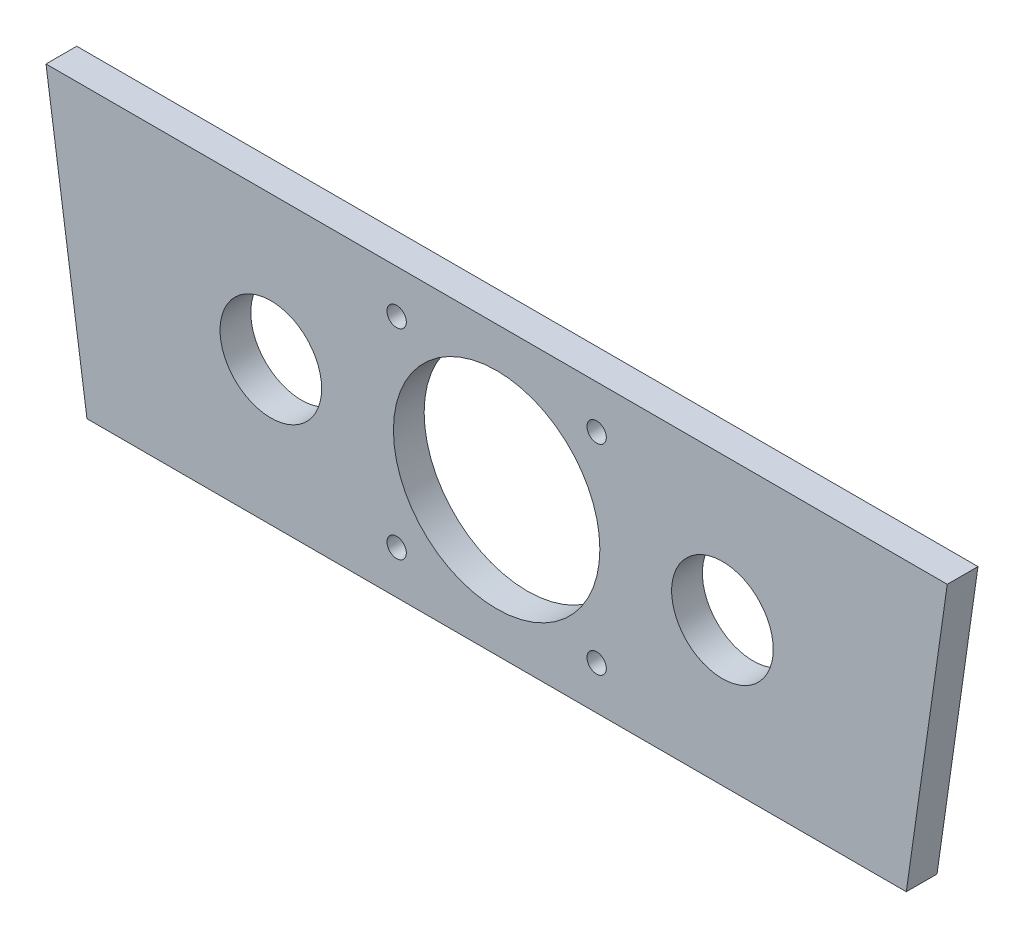
SolidWorks part; units mm, degrees
material "ASTM A36 Steel"
ref_plane "Front Plane" through (0, 0, 0) normal (0, 0, 1) x (1, 0, 0)
ref_plane "Top Plane" through (0, 0, 0) normal (0, 1, 0) x (1, 0, 0)
ref_plane "Right Plane" through (0, 0, 0) normal (1, 0, 0) x (0, 0, -1)
sketch "Sketch2" plane through (0, 0, 0) normal (0, 0, 1) x (1, 0, 0)
  line L0 (0, 0) -> (152.4, 0)
  line L1 (76.2, 0) -> (76.2, 6.35) construction
  line L2 (139.7, 6.35) -> (12.7, 6.35)
  line L3 (12.7, 6.35) -> (6.35, 50.8)
  line L4 (6.35, 50.8) -> (0, 50.8)
  line L5 (0, 50.8) -> (0, 0)
  line L6 (152.4, 50.8) -> (152.4, 0)
  line L7 (146.05, 50.8) -> (152.4, 50.8)
  line L8 (139.7, 6.35) -> (146.05, 50.8)
  line L9 (12.7, 6.35) -> (12.7, 0) construction
  line L10 (12.7, 6.35) -> (0, 6.35) construction
  line L11 (146.05, 50.8) -> (6.35, 50.8)
  line L12 (9.525, 28.575) -> (142.875, 28.575) construction
  line L13 (76.2, 50.8) -> (76.2, 6.35) construction
  line L14 (60.7, 13.075) -> (60.7, 28.575) construction
  line L15 (60.7, 13.075) -> (76.2, 13.075) construction
  circle A0 centre (60.7, 13.075) radius 1.5
  circle A1 centre (91.7, 13.075) radius 1.5
  circle A2 centre (60.7, 44.075) radius 1.5
  circle A3 centre (91.7, 44.075) radius 1.5
  circle A4 centre (76.2, 28.575) radius 16
  circle A5 centre (111.2, 28.575) radius 7.874
  circle A6 centre (41.2, 28.575) radius 7.874
  point P30 (92.2, 28.575)
  point P31 (103.326, 28.575)
  dimension "D6" = 3
  dimension "D7" = 32
  dimension "D8" = 15.748
  dimension "D1" = 152.4
  dimension "D2" = 50.8
  dimension "D3" = 6.35
  dimension "D4" = 12.7
  dimension "D5" = 15.5
  dimension "D9" = 35
extrude "Boss-Extrude1" add sketch "Sketch2" along normal blind 4.7625 contours L8 L2 L3 L4 L5 L0 L6 L7 region at (1.6064, 25.4, 0)
extrude "Boss-Extrude2" add sketch "Sketch2<3>" along normal up to surface (4.7625 mm away) contours L8 L11 L3 L2 region at (76.2, 49.334, 0) up to face at (76.2, 26.9875, 4.7625)
sketch "Sketch2<3>" plane through (0, 0, 0) normal (0, 0, 1) x (1, 0, 0) same geometry as "Sketch2"
extrude "Cut-Extrude1" cut sketch "Sketch2<4>" along normal up to surface (4.7625 mm away) contours L8 L2 L3 L4 L5 L0 L6 L7 region at (1.6064, 25.4, 0) up to face at (76.2, 25.4, 4.7625)
sketch "Sketch2<4>" plane through (0, 0, 0) normal (0, 0, 1) x (1, 0, 0) same geometry as "Sketch2"
